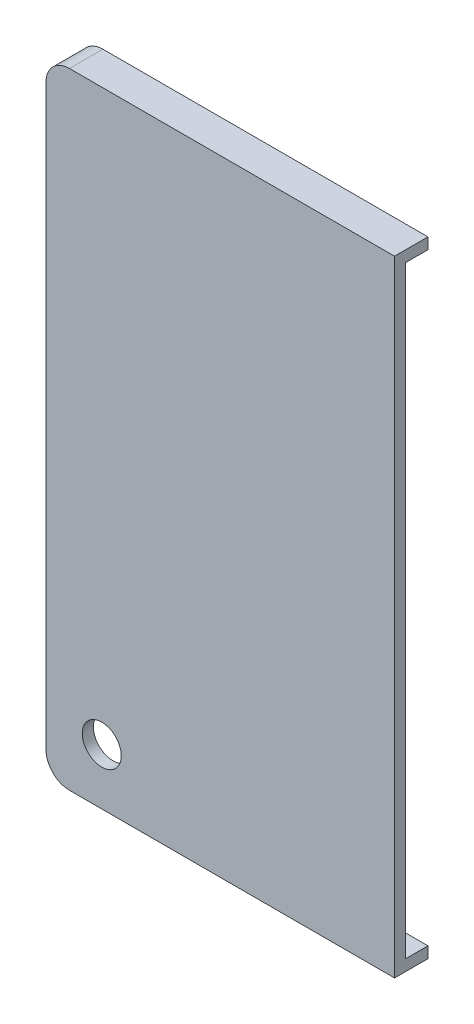
SolidWorks part; units mm, degrees
ref_plane "Front Plane" through (0, 0, 0) normal (0, 0, 1) x (1, 0, 0)
ref_plane "Top Plane" through (0, 0, 0) normal (0, 1, 0) x (1, 0, 0)
ref_plane "Right Plane" through (0, 0, 0) normal (1, 0, 0) x (0, 0, -1)
sketch "Sketch1" plane through (0, 0, 0) normal (0, 0, 1) x (1, 0, 0)
  line L4 (657.3112, -1230.231) -> (657.3112, -1334.011)
  line L5 (661.5112, -1338.211) -> (719.8512, -1338.211)
  line L7 (719.8512, -1226.031) -> (661.5112, -1226.031)
  line L8 (659.3112, -1230.231) -> (659.3112, -1334.011)
  line L9 (661.5112, -1336.211) -> (769.8512, -1336.211)
  line L10 (772.0512, -1334.011) -> (772.0512, -1230.231)
  line L11 (769.8512, -1228.031) -> (661.5112, -1228.031)
  line L12 (659.3112, -1230.231) -> (659.3112, -1334.011)
  line L13 (661.5112, -1336.211) -> (719.8512, -1336.211)
  line L15 (719.8512, -1228.031) -> (661.5112, -1228.031)
  line L16 (719.8512, -1327.661) -> (719.8512, -1261.621) construction
  line L17 (719.8512, -1327.661) -> (719.8512, -1261.621)
  line L18 (719.8512, -1261.621) -> (719.8512, -1226.031)
  line L19 (719.8512, -1327.661) -> (719.8512, -1338.211)
  line L20 (769.8512, -1226.031) -> (661.5112, -1226.031) construction
  line L21 (769.8512, -1228.031) -> (661.5112, -1228.031) construction
  line L22 (661.5112, -1336.211) -> (769.8512, -1336.211) construction
  line L23 (661.5112, -1338.211) -> (769.8512, -1338.211) construction
  line L24 (772.0512, -1334.011) -> (772.0512, -1230.231) construction
  line L25 (774.0512, -1334.011) -> (774.0512, -1230.231) construction
  arc A4 (657.3112, -1334.011) -> (661.5112, -1338.211) centre (661.5112, -1334.011) ccw
  arc A7 (661.5112, -1226.031) -> (657.3112, -1230.231) centre (661.5112, -1230.231) ccw
  arc A8 (659.3112, -1334.011) -> (661.5112, -1336.211) centre (661.5112, -1334.011) ccw
  arc A9 (769.8512, -1336.211) -> (772.0512, -1334.011) centre (769.8512, -1334.011) ccw
  arc A10 (772.0512, -1230.231) -> (769.8512, -1228.031) centre (769.8512, -1230.231) ccw
  arc A11 (661.5112, -1228.031) -> (659.3112, -1230.231) centre (661.5112, -1230.231) ccw
  arc A12 (659.3112, -1334.011) -> (661.5112, -1336.211) centre (661.5112, -1334.011) ccw
  arc A15 (661.5112, -1228.031) -> (659.3112, -1230.231) centre (661.5112, -1230.231) ccw
  arc A20 (774.0512, -1230.231) -> (769.8512, -1226.031) centre (769.8512, -1230.231) ccw construction
  arc A21 (772.0512, -1230.231) -> (769.8512, -1228.031) centre (769.8512, -1230.231) ccw construction
  arc A22 (769.8512, -1338.211) -> (774.0512, -1334.011) centre (769.8512, -1334.011) ccw construction
  arc A23 (769.8512, -1336.211) -> (772.0512, -1334.011) centre (769.8512, -1334.011) ccw construction
  dimension "D2" = 2
extrude "Boss-Extrude1" add sketch "Sketch1" along normal blind 2 contours A15 L15 L18 L7 A7 L4 A4 L5 L19 L13 A12 L12 | L15 A15 L12 A12 L13 L19 L17 L18 region at (659.4496, -1228.1693, 0) region at (689.5907, -1282.121, 0)
extrude "Boss-Extrude2" add sketch "Sketch1<3>" against normal blind 4 contours A15 L15 L18 L7 A7 L4 A4 L5 L19 L13 A12 L12 region at (659.4496, -1228.1693, 0)
sketch "Sketch1<3>" plane through (0, 0, 0) normal (0, 0, 1) x (1, 0, 0) same geometry as "Sketch1"
sketch "Sketch2" plane through (0, 0, 2) normal (0, 0, 1) x (1, 0, 0)
  line L0 (657.3112, -1328.211) -> (667.3112, -1328.211)
  line L1 (657.3112, -1230.231) -> (657.3112, -1334.011) construction
  line L2 (667.3112, -1328.211) -> (667.3112, -1338.211)
  line L3 (661.5112, -1338.211) -> (719.8512, -1338.211) construction
  circle A0 centre (667.3112, -1328.211) radius 3.5
  dimension "D3" = 7
  dimension "D1" = 10
  dimension "D2" = 10
extrude "Cut-Extrude1" cut sketch "Sketch2" against normal up to surface (2 mm away) contours L2 A0 L0 | L0 A0 L2 region at (667.8064, -1327.7158, 2) region at (665.8258, -1329.6964, 2) up to face at (680.0727, -1282.121, 0)
equation "\"C\"=0.2"
equation "\"D1@Sketch1\"=\"C\""
equation "\"T\"=2"
equation "\"D2@Sketch1\"=\"T\""
equation "\"D1@Boss-Extrude1\"=\"T\""
equation "\"HANG\"=4"
equation "\"D2@Boss-Extrude1\"=\"HANG\""
equation "\"D1@Boss-Extrude2\"=\"HANG\""
equation "\"OFF1\"=10"
equation "\"D1@Sketch2\"=\"OFF1\""
equation "\"OFF2\"=10"
equation "\"D2@Sketch2\"=\"OFF2\""
equation "\"HOLED\"=7"
equation "\"D3@Sketch2\"=\"HOLED\""
